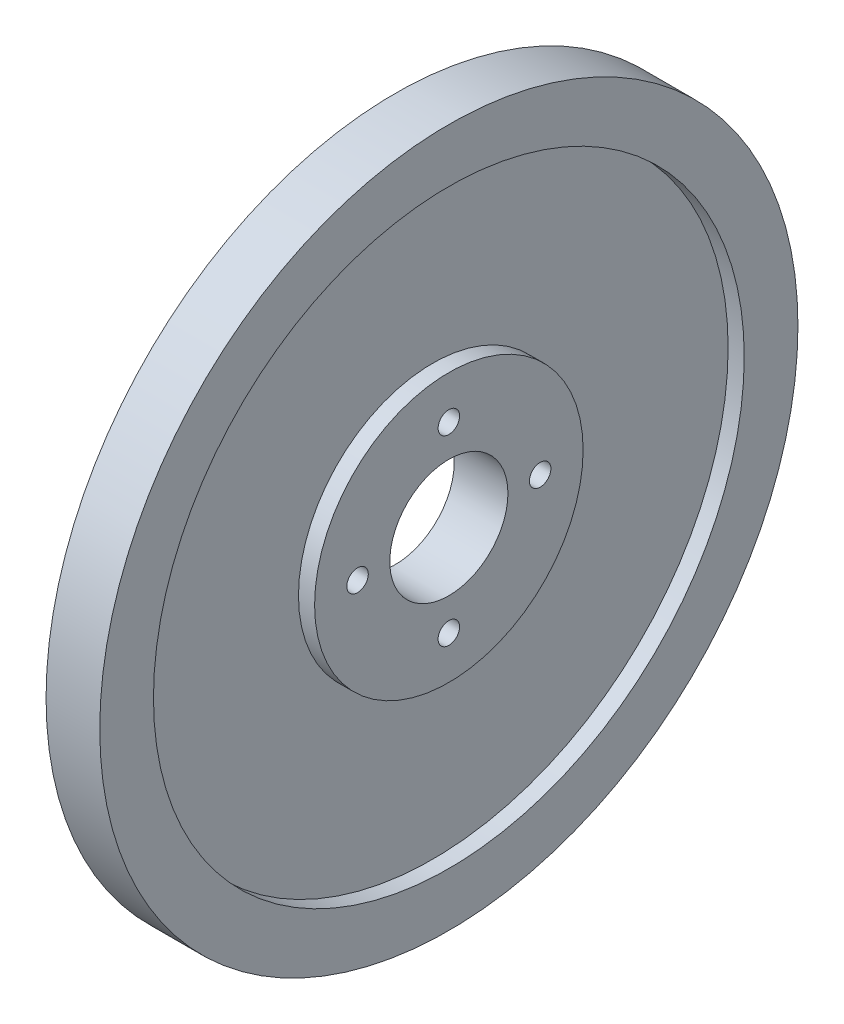
SolidWorks part; units mm, degrees
material "2024-T4"
ref_plane "Front Plane" through (0, 0, 0) normal (0, 0, 1) x (1, 0, 0)
ref_plane "Top Plane" through (0, 0, 0) normal (0, 1, 0) x (1, 0, 0)
ref_plane "Right Plane" through (0, 0, 0) normal (1, 0, 0) x (0, 0, -1)
sketch "Sketch1" plane through (0, 0, 0) normal (1, 0, 0) x (0, 0, -1)
  circle A1 centre (0, 0) radius 65
  dimension "D1" = 130
extrude "Boss-Extrude1" add sketch "Sketch1" along normal mid plane 10
sketch "Sketch3" plane through (5, 0, 0) normal (1, 0, 0) x (0, 0, -1)
  circle A0 centre (0, 0) radius 11
  dimension "D1" = 22
extrude "Cut-Extrude2" cut sketch "Sketch3" against normal through all
sketch "Sketch4" [suppressed] plane through (5, 0, 0) normal (1, 0, 0) x (0, 0, -1)
  line L0 (0, 0) -> (0, 5) construction
  circle A1 centre (0, 5) radius 1.5
  circle A2 centre (5, 0) radius 1.5
  circle A3 centre (0, -5) radius 1.5
  circle A4 centre (-5, 0) radius 1.5
  point P13 (0, 0)
  dimension "D1" = 5
  dimension "D2" = 3
  dimension "D3" = 4
extrude "Cut-Extrude3" [suppressed] cut sketch "Sketch4" against normal through all
sketch "Sketch5" plane through (5, 0, 0) normal (1, 0, 0) x (0, 0, -1)
  line L0 (0, 0) -> (0, 17) construction
  circle A2 centre (0, 17) radius 2
  circle A3 centre (17, 0) radius 2
  circle A4 centre (0, -17) radius 2
  circle A5 centre (-17, 0) radius 2
  point P12 (0, 0)
  dimension "D2" = 4
  dimension "D1" = 17
  dimension "D4" = 17
  dimension "D5" = 17
  dimension "D3" = 4
sketch "Sketch6" [suppressed] plane through (5, 0, 0) normal (1, 0, 0) x (0, 0, -1)
  line L0 (0, 0) -> (0, 33.7163) construction
  circle A12 centre (0, 0) radius 16
  circle A13 centre (0, 0) radius 55
  point P35 (0, 0)
  dimension "D1" = 110
  dimension "D2" = 32
extrude "Cut-Extrude4" [suppressed] cut sketch "Sketch6" against normal blind 3 contours A13 A12
extrude "Cut-Extrude5" cut sketch "Sketch5" against normal through all contours A2 | A5 | A4 | A3
sketch "Sketch7" [suppressed] plane through (5, 0, 0) normal (1, 0, 0) x (0, 0, -1)
  circle A0 centre (0, 0) radius 8
  dimension "D1" = 16
extrude "Cut-Extrude6" [suppressed] cut sketch "Sketch7" against normal through all
ref_plane "Plane1" [suppressed] through (0, 0, 0) normal (1, 0, 0) x (0, 0, -1)
sketch "Sketch8" [suppressed] plane through (0, 0, 0) normal (1, 0, 0) x (0, 0, -1)
  circle A0 centre (0, 0) radius 6.5
  circle A1 centre (0, 0) radius 8 construction
  circle A2 centre (0, 0) radius 8
  dimension "D1" = 13
extrude "Boss-Extrude2" [suppressed] add sketch "Sketch8" along normal mid plane 1.5
mirror "Mirror1" [suppressed] about plane through (0, 0, 0) normal (1, 0, 0)
sketch "Sketch9" plane through (5, 0, 0) normal (1, 0, 0) x (0, 0, -1)
  circle A0 centre (0, 0) radius 25
  circle A1 centre (0, 0) radius 55
  dimension "D1" = 110
  dimension "D2" = 50
extrude "Cut-Extrude7" cut sketch "Sketch9" against normal blind 3
mirror "Mirror2" about plane through (0, 0, 0) normal (1, 0, 0) of "Cut-Extrude7"
